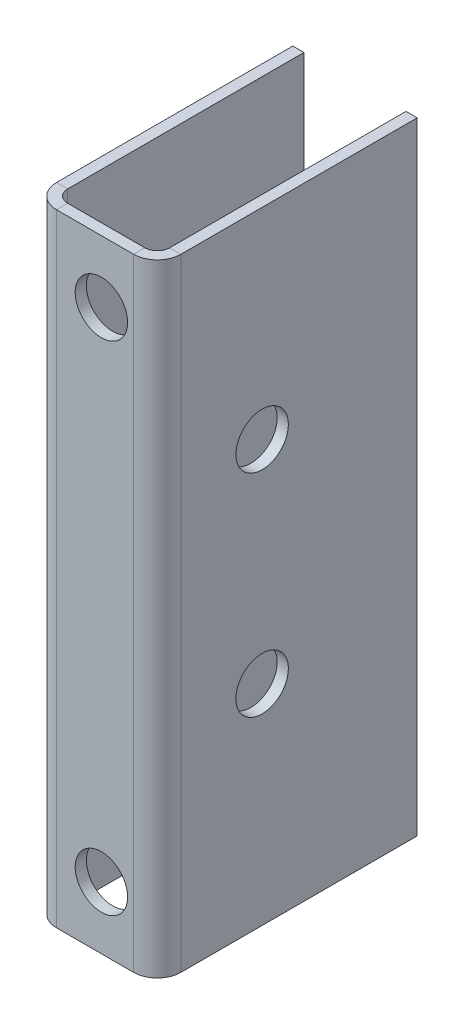
SolidWorks part; units mm, degrees
note: The reader was unsure of these and kept them because the rebuilt part matched: thickness of "Base-Flange1", "Edge-Flange2", "Edge-Flange5", "Sheet-Metal1", "Sheet-Metal3", "Sheet-Metal6", "Sheet-Metal7", "Sheet-Metal8"; flange length of "Edge-Flange2", "Edge-Flange5".
ref_plane "Front Plane" through (0, 0, 0) normal (0, 0, 1) x (1, 0, 0)
ref_plane "Top Plane" through (0, 0, 0) normal (0, 1, 0) x (1, 0, 0)
ref_plane "Right Plane" through (0, 0, 0) normal (1, 0, 0) x (0, 0, -1)
sketch "Sketch1" plane through (0, 0, 0) normal (0, 0, 1) x (1, 0, 0)
  line L0 (-4.3443, 45.5271) -> (-4.3443, -4.4729) construction
  line L1 (-8.4443, 45.5271) -> (-0.2443, 45.5271)
  line L2 (-8.4443, 45.5271) -> (-8.4443, -4.4729)
  line L3 (-8.4443, -4.4729) -> (-0.2443, -4.4729)
  line L4 (-0.2443, 45.5271) -> (-0.2443, -4.4729)
  line L5 (-8.4443, 20.5271) -> (-0.2443, 20.5271) construction
  dimension "D1" = 8.2
  dimension "D2" = 50
base flange "Base-Flange1" sketch "Sketch1" thickness 0.9 reverse thickness direction no parameters "D1"=1
edge flange "Edge-Flange2" sketch "Sketch11" flange angle 90 flange length 20 flange position material outside bend radius 1 thickness 0.9 parameters "D6"=10
sketch "Sketch11" plane through (-8.4443, 0, -0.9) normal (-1, 0, 0) x (0, 1, 0)
  line L0 (45.5271, 0) -> (-4.4729, 0) construction
  line L1 (45.5271, 0) -> (-4.4729, 0)
  line L2 (-4.4729, 0) -> (-4.4729, 20)
  line L3 (-4.4729, 20) -> (45.5271, 20)
  line L4 (45.5271, 20) -> (45.5271, 0)
bend "EdgeBend2" bend radius 1 bend angle 90 parameters "D5"=2
edge flange "Edge-Flange5" sketch "Sketch21" flange angle 90 flange length 20 flange position material outside bend radius 1 thickness 0.9 parameters "D6"=10
sketch "Sketch21" plane through (-0.2443, 0, -0.9) normal (-1, 0, 0) x (0, 1, 0)
  line L2 (-4.4729, 0) -> (-4.4729, 20)
  line L3 (-4.4729, 20) -> (45.5271, 20)
  line L4 (45.5271, 20) -> (45.5271, 0)
  line L6 (45.5271, 0) -> (-4.4729, 0) construction
  line L7 (45.5271, 0) -> (-4.4729, 0)
bend "EdgeBend5" bend radius 1 bend angle 90 parameters "D5"=3
hole_wizard "#19 (0.166) Diameter Slot1" positions "Sketch23" profile "Sketch22" size "#19" standard "ANSI Inch" slot yes end condition through all
sketch "Sketch23" plane through (0, 0, -0.9) normal (0, 0, -1) x (-1, 0, 0)
  line L0 (1.2443, 45.5271) -> (7.4443, 45.5271) construction
  line L1 (7.4443, -4.4729) -> (1.2443, -4.4729) construction
  point P0 (3.836, 40.5271)
  point P2 (3.836, 0.5271)
  dimension "D1" = 5
  dimension "D2" = 5
sketch "Sketch22" plane through (-3.836, 40.5271, -0.9) normal (1, 0, 0) x (0, 1, 0)
  line L0 (0, 0) -> (0, 0.9)
  line L1 (0, 0.9) -> (2.1082, 0.9)
  line L2 (2.1082, 0.9) -> (2.1082, 0)
  line L5 (2.1082, 0) -> (0, 0)
  line L11 (0, -6.35) -> (0, 107.95) construction
  dimension "Thru Hole Dia." = 4.2164
  dimension "Thru Hole Depth" = 0.9
hole_wizard "#19 (0.166) Diameter Slot2" positions "Sketch25" profile "Sketch24" size "#19" standard "ANSI Inch" slot yes end condition through all
sketch "Sketch25" plane through (0.6557, 0, 0) normal (1, 0, 0) x (0, 0, -1)
  point P0 (8.4321, 29.3673)
  point P3 (8.4321, 12.3673)
  point P6 (8.4321, 29.3673)
  point P8 (8.4321, 12.3673)
sketch "Sketch24" plane through (0.6557, 29.3673, -8.4321) normal (0, 1, 0) x (0, 0, -1)
  line L0 (0, 0) -> (0, 10)
  line L1 (0, 10) -> (2.1082, 10)
  line L2 (2.1082, 10) -> (2.1082, 0)
  line L5 (2.1082, 0) -> (0, 0)
  line L11 (0, -6.35) -> (0, 107.95) construction
  dimension "Thru Hole Dia." = 4.2164
  dimension "Thru Hole Depth" = 10
sketch "Bend-Lines1" plane through (0, 0, 0) normal (0, 1, 0) x (1, 0, 0)
sketch "Bounding-Box1" plane through (0, 0, 0) normal (0, 1, 0) x (1, 0, 0)
sheet metal parameters "Sheet-Metal1" thickness 0.9 parameters "D1"=1
flat pattern "Flat-Pattern1" [suppressed]
sketch "Bend-Lines2" plane through (0, 0, 0) normal (0, 1, 0) x (1, 0, 0)
sketch "Bounding-Box2" [suppressed] plane through (0, 0, 0) normal (0, 1, 0) x (1, 0, 0)
sheet metal parameters "Sheet-Metal3" thickness 0.9 parameters "D1"=1
flat pattern "Flat-Pattern1" [suppressed]
sketch "Bend-Lines2" plane through (0, 0, 0) normal (0, 1, 0) x (1, 0, 0)
sketch "Bounding-Box2" [suppressed] plane through (0, 0, 0) normal (0, 1, 0) x (1, 0, 0)
bend of the flat pattern "Flatten-<EdgeBend2>1"
sheet metal parameters "Sheet-Metal6" thickness 0.9 parameters "D1"=1
flat pattern "Flat-Pattern1" [suppressed]
sketch "Bend-Lines2" plane through (0, 0, 0) normal (0, 1, 0) x (1, 0, 0)
sketch "Bounding-Box2" [suppressed] plane through (0, 0, 0) normal (0, 1, 0) x (1, 0, 0)
bend of the flat pattern "Flatten-<EdgeBend2>1"
bend of the flat pattern "Flatten-<EdgeBend5>1"
sheet metal parameters "Sheet-Metal7" thickness 0.9 parameters "D1"=1
flat pattern "Flat-Pattern1" [suppressed]
sketch "Bend-Lines2" plane through (0, 0, 0) normal (0, 1, 0) x (1, 0, 0)
sketch "Bounding-Box2" [suppressed] plane through (0, 0, 0) normal (0, 1, 0) x (1, 0, 0)
bend of the flat pattern "Flatten-<EdgeBend2>1"
bend of the flat pattern "Flatten-<EdgeBend5>1"
sheet metal parameters "Sheet-Metal8" thickness 0.9 parameters "D1"=1
flat pattern "Flat-Pattern1" [suppressed]
sketch "Bend-Lines2" plane through (0, 0, 0) normal (0, 1, 0) x (1, 0, 0)
sketch "Bounding-Box2" [suppressed] plane through (0, 0, 0) normal (0, 1, 0) x (1, 0, 0)
bend of the flat pattern "Flatten-<EdgeBend2>1"
bend of the flat pattern "Flatten-<EdgeBend5>1"
equation "\"20mmmm\"=1"
